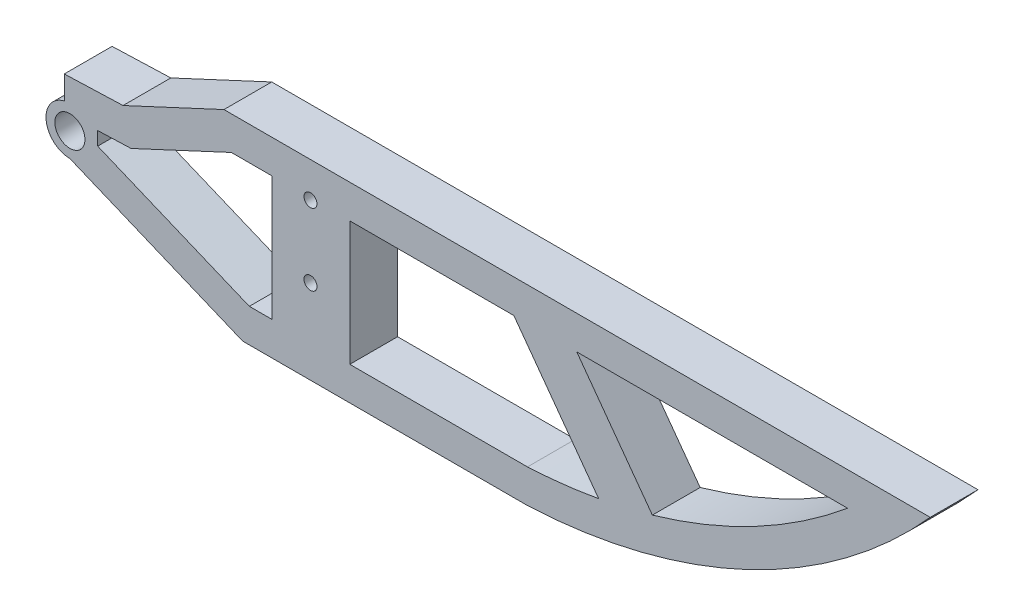
SolidWorks part; units mm, degrees
ref_plane "Front Plane" through (0, 0, 0) normal (0, 0, 1) x (1, 0, 0)
ref_plane "Top Plane" through (0, 0, 0) normal (0, 1, 0) x (1, 0, 0)
ref_plane "Right Plane" through (0, 0, 0) normal (1, 0, 0) x (0, 0, -1)
sketch "Sketch1" plane through (0, 0, 0) normal (0, 0, 1) x (1, 0, 0)
  line L1 (120.65, 25.4) -> (-120.65, 25.4)
  line L2 (120.65, 25.4) -> (120.65, -25.4)
  line L3 (120.65, -25.4) -> (-120.65, -25.4)
  line L4 (-120.65, 25.4) -> (-120.65, -25.4)
  line L5 (120.65, 25.4) -> (-120.65, -25.4) construction
  line L6 (120.65, -25.4) -> (-120.65, 25.4) construction
  point P0 (0, 0)
  dimension "D1" = 241.3
  dimension "D2" = 50.8
extrude "Boss-Extrude1" add sketch "Sketch1" along normal blind 12.7
sketch "Sketch3" plane through (0, 0, 12.7) normal (0, 0, 1) x (1, 0, 0)
  line L0 (0, 0) -> (-120.65, 0) construction
  line L1 (-120.65, 25.4) -> (-120.65, -25.4) construction
  circle A0 centre (-107.95, 0) radius 4
  dimension "D2" = 8
  dimension "D1" = 12.7
extrude "Cut-Extrude1" cut sketch "Sketch3" against normal through all
sketch "Sketch5" plane through (0, 0, 12.7) normal (0, 0, 1) x (1, 0, 0)
  line L0 (-120.65, -25.4) -> (120.65, -25.4) construction
  line L1 (-107.95, -6.35) -> (-62.0461, -25.4)
  line L2 (-107.95, 6.35) -> (-67.0151, 25.4)
  line L3 (120.65, 25.4) -> (-120.65, 25.4) construction
  line L4 (-67.0151, 25.4) -> (-120.65, 25.4)
  line L5 (-120.65, 25.4) -> (-120.65, -25.4)
  line L6 (-120.65, -25.4) -> (-62.0461, -25.4)
  line L7 (120.65, 25.4) -> (120.65, -25.4)
  line L8 (120.65, -25.4) -> (0, -25.4)
  arc A0 (0, -25.4) -> (120.65, 25.4) centre (6.9175, 126.8429) ccw
  arc A2 (-107.95, 6.35) -> (-107.95, -6.35) centre (-107.95, 0) ccw
  line M3 (-120.65, 25.4) -> (-120.65, -25.4)
  line M4 (-120.65, -25.4) -> (120.65, -25.4)
  line M5 (120.65, -25.4) -> (120.65, 25.4)
  line M6 (120.65, 25.4) -> (-120.65, 25.4)
  dimension "D1" = 152.4
  dimension "D2" = 12.7
extrude "Cut-Extrude2" cut sketch "Sketch5" against normal through all contours A2 L2 L1 M6 M3 M4 | A0 L8 M5 region at (-85.2953, -16.5913, 12.7) region at (93.5193, -10.6939, 12.7)
sketch "Sketch6" plane through (0, 0, 12.7) normal (0, 0, 1) x (1, 0, 0)
  line L0 (-107.95, 0) -> (91.396, 0) construction
  arc A0 (13.8349, -25.4) -> (120.65, 25.4) centre (6.9175, 126.8429) ccw construction
  circle A1 centre (19.05, 0) radius 3.1347
  dimension "D1" = 127
sketch "Sketch7" plane through (0, 0, 0) normal (0, 0, -1) x (-1, 0, 0)
  line L0 (44.0204, -2.9977) -> (44.0204, 16.0523) construction
  point P3 (44.0204, -2.9977)
  point P4 (44.0204, 16.0523)
  dimension "D1" = 19.05
sketch "Sketch8" plane through (0, 0, 0) normal (0, 0, -1) x (-1, 0, 0)
  point P0 (44.0204, 16.0523)
  point P3 (44.0204, -2.9977)
hole_wizard "Tap Drill for #8-32 Tap1" positions "Sketch8" profile "Sketch9" hole size "#8-32" standard "ANSI Inch" end condition through all
sketch "Sketch9" plane through (-44.0204, 16.0523, 0) normal (1, 0, 0) x (0, 1, 0)
  line L0 (0, 0) -> (0, 12.7)
  line L1 (0, 12.7) -> (1.7272, 12.7)
  line L2 (1.7272, 12.7) -> (1.7272, 0)
  line L5 (1.7272, 0) -> (0, 0)
  line L11 (0, -6.35) -> (0, 107.95) construction
  dimension "Thru Hole Dia." = 3.4544
  dimension "Thru Hole Depth" = 12.7
ref_plane "Plane1" through (-114.3, 0, 0) normal (-1, 0, 0) x (0, 0, 1)
sketch "Sketch10" plane through (-114.3, 0, 0) normal (-1, 0, 0) x (0, 0, 1)
  line L0 (0, 0) -> (12.7, 0) construction
  line L1 (12.7, -3.1347) -> (12.7, 3.1347) construction
  circle A0 centre (6.0894, 0) radius 1.905
  dimension "D1" = 3.81
extrude "Cut-Extrude3" cut sketch "Sketch10" against normal blind 5.08
sketch "Sketch11" plane through (0, 0, 12.7) normal (0, 0, 1) x (1, 0, 0)
  line L0 (-93.8249, 12.9234) -> (-109.4459, 12.9234) construction
  line L1 (-107.95, 6.35) -> (-67.0151, 25.4) construction
  line L2 (-109.4459, 12.9234) -> (-109.4459, 5.6538) construction
  line L3 (-93.8249, 12.9234) -> (-109.4459, 5.6538)
  line L4 (-93.8249, 12.9234) -> (-109.4459, 12.3779)
  line L5 (-109.4459, 12.3779) -> (-109.4459, 5.6538)
  circle A1 centre (-107.95, 0) radius 4 construction
  dimension "D1" = 15.621
  dimension "D2" = 5.6538
  dimension "D3" = 178
extrude "Boss-Extrude2" add sketch "Sketch11" against normal up to surface (12.7 mm away) up to face at (-45.7476, 16.0523, 0)
sketch "Sketch12" plane through (0, 0, 12.7) normal (0, 0, 1) x (1, 0, 0)
  line L1 (10.0217, 16.51) -> (-33.5733, 16.51)
  line L24 (-33.5733, 16.51) -> (-33.5733, -16.51)
  line L25 (-54.2244, 16.51) -> (-54.2244, -16.51)
  line L26 (-54.2244, 16.51) -> (-65.0478, 16.51)
  line L27 (-33.5733, -16.51) -> (13.63, -16.51)
  line L28 (10.0217, 16.51) -> (32.5572, -14.3581)
  line L29 (26.7339, 16.51) -> (46.8231, -11.0072)
  line L30 (-100.5559, 3.793) -> (-100.5559, 0.2066)
  line L31 (-100.5559, 0.2066) -> (-60.2747, -16.51)
  line L32 (-60.2747, -16.51) -> (13.63, -16.51)
  line L33 (98.6876, 16.51) -> (-65.0478, 16.51)
  line L34 (-65.0478, 16.51) -> (-91.7106, 4.1018)
  line L35 (-91.7106, 4.1018) -> (-100.5559, 3.793)
  line L36 (-100.5559, 3.793) -> (-100.5559, 0.2066)
  line L37 (-100.5559, 0.2066) -> (-60.2747, -16.51)
  line L38 (-60.2747, -16.51) -> (-54.2244, -16.51)
  line L39 (98.6876, 16.51) -> (26.7339, 16.51)
  line L40 (-65.0478, 16.51) -> (-91.7106, 4.1018)
  line L41 (-91.7106, 4.1018) -> (-100.5559, 3.793)
  arc A0 (46.8231, -11.0072) -> (98.6876, 16.51) centre (6.9175, 126.8429) ccw
  arc A10 (13.63, -16.51) -> (98.6876, 16.51) centre (6.9175, 126.8429) ccw
  arc A11 (13.63, -16.51) -> (32.5572, -14.3581) centre (6.9175, 126.8429) ccw
  dimension "D1" = 8.89
extrude "Cut-Extrude4" cut sketch "Sketch12" against normal through all
